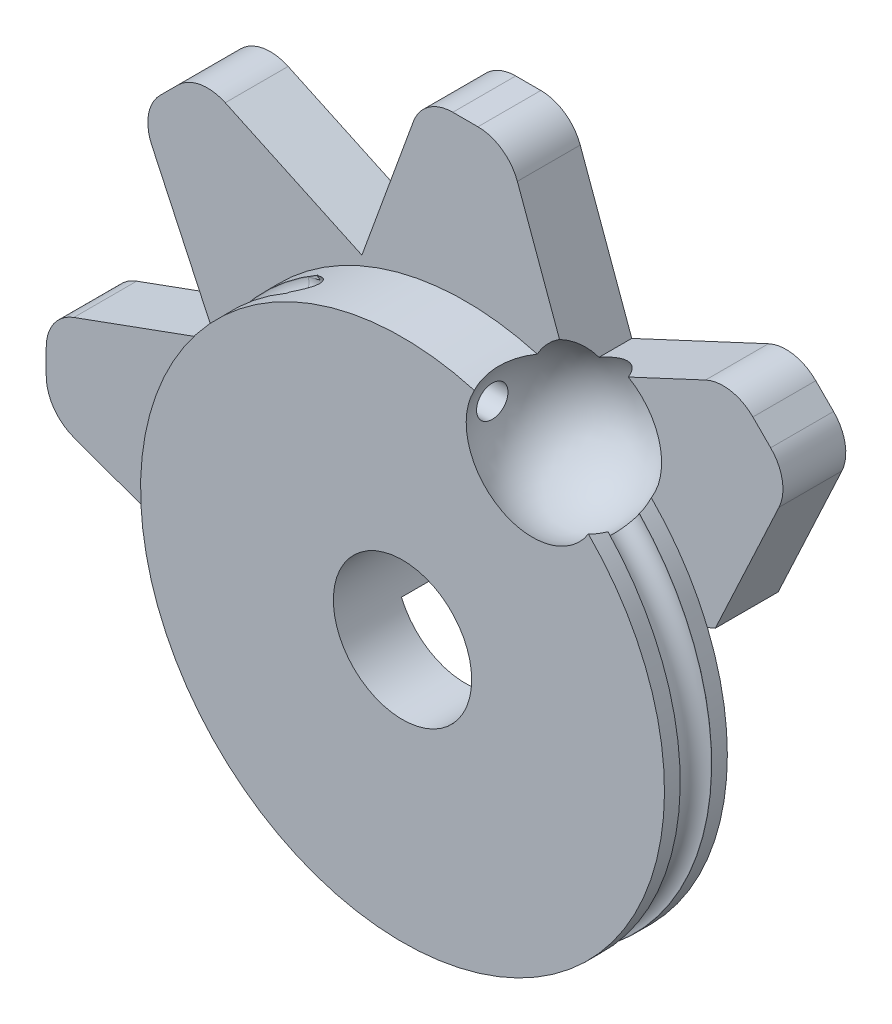
SolidWorks part; units mm, degrees
ref_plane "Front Plane" through (0, 0, 0) normal (0, 0, 1) x (1, 0, 0)
ref_plane "Top Plane" through (0, 0, 0) normal (0, 1, 0) x (1, 0, 0)
ref_plane "Right Plane" through (0, 0, 0) normal (1, 0, 0) x (0, 0, -1)
ref_axis "Axis1" through (-10.8788, 0, 0) along (1, 0, 0)
ref_axis "Axis2" through (0, 0, 2.0438) along (0, 0, -1)
ref_plane "Plane5" through (0, 0, 0) normal (0.866, 0.5, 0) x (0, 0, -1)
ref_plane "Plane6" through (3.1, 0, 0) normal (1, 0, 0) x (0, 0, -1)
sketch "Sketch1" plane through (0, 0, 0) normal (0, 0, 1) x (1, 0, 0)
  line L0 (-10.8788, 0) -> (8.4547, 0) construction
  circle A0 centre (0, 0) radius 6.25
  dimension "D1" = 12.5
extrude "body" add sketch "Sketch1" along normal blind 1.5 contours A0
sketch "Sketch2" plane through (0, 0, 0) normal (1, 0, 0) x (0, 0, -1)
  line L1 (0, 6.25) -> (-1.5, 6.25) construction
  line L2 (0, 5.25) -> (-1.5, 5.25) construction
  line L3 (-0.75, 5.25) -> (-0.75, -4.75) construction
  line L4 (0, -6.25) -> (0, 6.25) construction
  line L5 (0, -6.25) -> (0, 6.25) construction
  circle A0 centre (-0.75, 5.25) radius 0.375
  circle A1 centre (-0.75, -4.75) radius 0.375
  dimension "D1" = 0.75
  dimension "D3" = 0.75
  dimension "D4" = 1.5
  dimension "D2" = 1
extrude "Hole to trap cable knot" cut sketch "Sketch2" against normal through all and the other way blind 10 contours A0 | A1
ref_plane "Plane1" through (0, 0, 1.875) normal (0, 0, 1) x (1, 0, 0)
sketch "Sketch6" plane through (0, 0, 1.875) normal (0, 0, 1) x (1, 0, 0)
  line L0 (1.0209, -1.7683) -> (-1.0209, 1.7683) construction
  arc A0 (3.9111, 4.875) -> (2.7243, 5.625) centre (0, 0) ccw construction
  circle A2 centre (0, 0) radius 6.25 construction
  arc A3 (-3.125, 5.4127) -> (3.2608, 5.332) centre (0, 0) ccw
  arc A4 (3.9111, 4.875) -> (2.7243, 5.625) centre (0, 0) ccw construction
sketch "Sketch10" plane through (-5.4127, 9.375, 0) normal (-0.866, -0.5, 0) x (-0.5, 0.866, 0)
  line L0 (-4.5831, -1.125) -> (-3.8727, -1.125)
  line L1 (-3.8727, -1.125) -> (-3.8727, -0.3748)
  line L2 (-3.8727, -0.3748) -> (-4.5831, -0.3748)
  arc A0 (-4.5831, -0.3748) -> (-4.5831, -1.125) centre (-4.5831, -0.7499) ccw
  spline S0 degree 3 poles (-4.5903, -1.125) (-4.5759, -1.125) (-4.5739, -1.1025) (-4.5775, -1.0318) (-4.5799, -1.0018) (-4.5843, -0.9422) (-4.5859, -0.9199) (-4.589, -0.8665) (-4.5904, -0.8353) (-4.592, -0.7664) (-4.5919, -0.7281) (-4.5902, -0.6593) (-4.5887, -0.6289) (-4.5841, -0.5506) (-4.5809, -0.5129) (-4.5744, -0.422) (-4.574, -0.3902) (-4.5837, -0.3678) (-4.5938, -0.3778) (-4.6147, -0.4453) (-4.6227, -0.4771) (-4.6376, -0.5669) (-4.6447, -0.6281) (-4.6494, -0.7694) (-4.6461, -0.8461) (-4.6338, -0.9631) (-4.6257, -1.0065) (-4.603, -1.1026) (-4.5903, -1.125) (-4.5759, -1.125) (-4.5739, -1.1025) knots -0.125 -0.125 0 0 0.125 0.125 0.1875 0.1875 0.21875 0.21875 0.25 0.25 0.28125 0.28125 0.3125 0.3125 0.375 0.375 0.5 0.5 0.625 0.625 0.6875 0.6875 0.75 0.75 0.8125 0.8125 0.875 0.875 1 1 1.125 1.125 1.1875 only from (-4.5831, -1.125) to (-4.5831, -1.125) construction
  spline S1 degree 3 poles (-4.5903, -1.125) (-4.5759, -1.125) (-4.5739, -1.1025) (-4.5775, -1.0318) (-4.5799, -1.0018) (-4.5843, -0.9422) (-4.5859, -0.9199) (-4.589, -0.8665) (-4.5904, -0.8353) (-4.592, -0.7664) (-4.5919, -0.7281) (-4.5902, -0.6593) (-4.5887, -0.6289) (-4.5841, -0.5506) (-4.5809, -0.5129) (-4.5744, -0.422) (-4.574, -0.3902) (-4.5837, -0.3678) (-4.5938, -0.3778) (-4.6147, -0.4453) (-4.6227, -0.4771) (-4.6376, -0.5669) (-4.6447, -0.6281) (-4.6494, -0.7694) (-4.6461, -0.8461) (-4.6338, -0.9631) (-4.6257, -1.0065) (-4.603, -1.1026) (-4.5903, -1.125) (-4.5759, -1.125) (-4.5739, -1.1025) knots -0.125 -0.125 0 0 0.125 0.125 0.1875 0.1875 0.21875 0.21875 0.25 0.25 0.28125 0.28125 0.3125 0.3125 0.375 0.375 0.5 0.5 0.625 0.625 0.6875 0.6875 0.75 0.75 0.8125 0.8125 0.875 0.875 1 1 1.125 1.125 1.1875 only from (-4.5831, -1.125) to (-4.5831, -1.125) construction
  point P1 (-4.5831, -0.3748)
sweep "track for cable" cut profiles "Sketch10" path "Sketch6"
sketch "Sketch12" plane through (0, 0, 0) normal (0, 0, -1) x (-1, 0, 0)
  line L0 (0, 10) -> (0, -10) construction
  line L1 (-2.5653, 5.6993) -> (-1.2395, 9.342)
  line L2 (-0.2998, 10) -> (0.2998, 10)
  line L3 (1.2395, 9.342) -> (2.5653, 5.6993)
  line L6 (-3.2365, 3.8554) -> (3.2365, 3.8554) construction
  line L7 (-2.5653, 5.6993) -> (0, 0)
  line L8 (0, 0) -> (2.5653, 5.6993)
  arc A0 (-1.2395, 9.342) -> (-0.2998, 10) centre (-0.2998, 9) cw
  arc A1 (0.2998, 10) -> (1.2395, 9.342) centre (0.2998, 9) cw
  circle A4 centre (0, 0) radius 6.25 construction
  point P9 (-1, 10)
  point P12 (1, 10)
  dimension "D6" = 1
  dimension "D1" = 20
  dimension "D2" = 2
  dimension "D3" = 6.4729
  dimension "D4" = 110
  dimension "D5" = 110
sketch "Sketch14" plane through (0, 0, 0) normal (0, 0, -1) x (-1, 0, 0)
  line L0 (5.7294, 7.4823) -> (2.4696, 5.9622)
  line L1 (7.2831, 6.8591) -> (6.8591, 7.2831)
  line L2 (5.9622, 2.4696) -> (7.4823, 5.7294)
  line L3 (0, 0) -> (5.844, 2.216) construction
  line L4 (2.216, 5.844) -> (0, 0) construction
  line L5 (-1.2395, 9.342) -> (-2.5653, 5.6993)
  line L6 (0.2998, 10) -> (-0.2998, 10)
  line L7 (2.5653, 5.6993) -> (1.2395, 9.342)
  line L8 (0, 0) -> (2.5653, 5.6993)
  line L9 (0, 0) -> (2.5653, 5.6993) construction
  line L10 (-1.2395, 9.342) -> (-2.4696, 5.9622)
  line L11 (0.2998, 10) -> (-0.2998, 10)
  line L12 (2.4696, 5.9622) -> (1.2395, 9.342)
  line L13 (-2.5653, 5.6993) -> (0, 0)
  line L14 (-2.5653, 5.6993) -> (0, 0) construction
  line L15 (9.342, 1.2395) -> (5.9622, 2.4696)
  line L16 (10, -0.2998) -> (10, 0.2998)
  line L17 (5.9622, -2.4696) -> (9.342, -1.2395)
  line L18 (0, 0) -> (5.6993, -2.5653) construction
  line L19 (5.6993, 2.5653) -> (0, 0) construction
  line L20 (7.4823, -5.7294) -> (5.9622, -2.4696) construction
  line L21 (6.8591, -7.2831) -> (7.2831, -6.8591) construction
  line L22 (2.4696, -5.9622) -> (5.7294, -7.4823) construction
  line L23 (0, 0) -> (2.216, -5.844) construction
  line L24 (5.844, -2.216) -> (0, 0) construction
  line L25 (1.2395, -9.342) -> (2.4696, -5.9622) construction
  line L26 (-0.2998, -10) -> (0.2998, -10) construction
  line L27 (-2.4696, -5.9622) -> (-1.2395, -9.342) construction
  line L28 (0, 0) -> (-2.5653, -5.6993) construction
  line L29 (2.5653, -5.6993) -> (0, 0) construction
  line L30 (-5.7294, -7.4823) -> (-2.4696, -5.9622) construction
  line L31 (-7.2831, -6.8591) -> (-6.8591, -7.2831) construction
  line L32 (-5.9622, -2.4696) -> (-7.4823, -5.7294) construction
  line L33 (0, 0) -> (-5.844, -2.216) construction
  line L34 (-2.216, -5.844) -> (0, 0) construction
  line L35 (-9.342, -1.2395) -> (-5.9622, -2.4696) construction
  line L36 (-10, 0.2998) -> (-10, -0.2998) construction
  line L37 (-5.9622, 2.4696) -> (-9.342, 1.2395) construction
  line L38 (0, 0) -> (-5.6993, 2.5653) construction
  line L39 (-5.6993, -2.5653) -> (0, 0) construction
  line L40 (-7.4823, 5.7294) -> (-5.9622, 2.4696)
  line L41 (-6.8591, 7.2831) -> (-7.2831, 6.8591)
  line L42 (-2.4696, 5.9622) -> (-5.7294, 7.4823)
  line L43 (0, 0) -> (-2.216, 5.844) construction
  line L44 (-5.844, 2.216) -> (0, 0) construction
  line L45 (5.9622, -2.4696) -> (-5.9622, 2.4696)
  arc A0 (6.8591, 7.2831) -> (5.7294, 7.4823) centre (6.152, 6.5759) ccw
  arc A1 (7.4823, 5.7294) -> (7.2831, 6.8591) centre (6.5759, 6.152) ccw
  arc A2 (-0.2998, 10) -> (-1.2395, 9.342) centre (-0.2998, 9) ccw
  arc A3 (1.2395, 9.342) -> (0.2998, 10) centre (0.2998, 9) ccw
  arc A4 (-0.2998, 10) -> (-1.2395, 9.342) centre (-0.2998, 9) ccw
  arc A5 (1.2395, 9.342) -> (0.2998, 10) centre (0.2998, 9) ccw
  arc A6 (10, 0.2998) -> (9.342, 1.2395) centre (9, 0.2998) ccw
  arc A7 (9.342, -1.2395) -> (10, -0.2998) centre (9, -0.2998) ccw
  arc A8 (7.2831, -6.8591) -> (7.4823, -5.7294) centre (6.5759, -6.152) ccw construction
  arc A9 (5.7294, -7.4823) -> (6.8591, -7.2831) centre (6.152, -6.5759) ccw construction
  arc A10 (0.2998, -10) -> (1.2395, -9.342) centre (0.2998, -9) ccw construction
  arc A11 (-1.2395, -9.342) -> (-0.2998, -10) centre (-0.2998, -9) ccw construction
  arc A12 (-6.8591, -7.2831) -> (-5.7294, -7.4823) centre (-6.152, -6.5759) ccw construction
  arc A13 (-7.4823, -5.7294) -> (-7.2831, -6.8591) centre (-6.5759, -6.152) ccw construction
  arc A14 (-10, -0.2998) -> (-9.342, -1.2395) centre (-9, -0.2998) ccw construction
  arc A15 (-9.342, 1.2395) -> (-10, 0.2998) centre (-9, 0.2998) ccw construction
  arc A16 (-7.2831, 6.8591) -> (-7.4823, 5.7294) centre (-6.5759, 6.152) ccw
  arc A17 (-5.7294, 7.4823) -> (-6.8591, 7.2831) centre (-6.152, 6.5759) ccw
  point P67 (0, 0)
  dimension "D1" = 0
  dimension "D2" = 8
extrude "thumb grip" add sketch "Sketch14" along normal blind 1.5
sketch "Sketch13" plane through (0, 0, 1.5) normal (0, 0, 1) x (1, 0, 0)
  circle A0 centre (0, 0) radius 1.65
  dimension "D1" = 3.3
extrude "hole for screw" cut sketch "Sketch13" against normal through all
sketch "Sketch20" plane through (3.1, 0, 0) normal (1, 0, 0) x (0, 0, -1)
  line L0 (-0.75, 7) -> (-0.75, 3.5)
  line L1 (-0.75, 7.7934) -> (-0.75, 1.6513) construction
  circle A0 centre (-0.75, 5.25) radius 1.75 construction
  arc A1 (-0.3841, 5.332) -> (-1.1159, 5.332) centre (-0.75, 5.25) ccw construction
  arc A2 (-0.3841, 5.332) -> (-1.1159, 5.332) centre (-0.75, 5.25) ccw construction
  arc A3 (-0.75, 7) -> (-0.75, 3.5) centre (-0.75, 5.25) cw
  dimension "D1" = 3.5
revolve "trap for ball" cut sketch "Sketch20" angle 360 about L1
sketch "Sketch21" plane through (0, 0, 1.5) normal (0, 0, 1) x (1, 0, 0)
  circle A0 centre (0, 0) radius 2.8716
  circle A3 centre (0, 0) radius 1.65 construction
  circle A4 centre (0, 0) radius 1.65
extrude "lip to contact handle" [suppressed] add sketch "Sketch21" along normal blind 0.25 and the other way blind 3.75
fillet "Fillet1" [suppressed] radius 0.1
equation "\"Do\"=8.5mm"
equation "\"Lo\"=10"
equation "\"screw_diam\"= 3.5mm"
equation "\"wheel_Do\"=12.5mm"
equation "\"wheel_thickness\"=4mm"
equation "\"Collet_diameter\"=4.3"
equation "\"clearance\"= 0.5mm"
equation "\"D1@Sketch1\"=\"wheel_Do\""
equation "\"wheel_total_diam_ent\"=20"
equation "\"D1@Sketch12\"=\"wheel_total_diam_ent\""
equation "\"handle_body_width\"= 10mm"
equation "\"finger_diameter\"=35"
equation "\"collet_lid_diameter\"=10"
equation "\"screw_cap_diam\"=5.15"
equation "\"handle_thickness\"=12.5mm"
equation "\"post_hole_diam\"=2"
equation "\"roll_rod_diam\"= 6.5 "
equation "\"roll_rod_length\"=6.6"
equation "\"disc_diam\"=5"
equation "\"disc_width\"=1.5"
equation "\"arm_width\"=5"
equation "\"arm_thickness\"=4.5"
equation "\"wheel_total_diam\"=30"
equation "\"D1@thumb grip\"=\"wheel_thickness\"-2.5"
equation "\"D1@body\"=\"wheel_thickness\""
